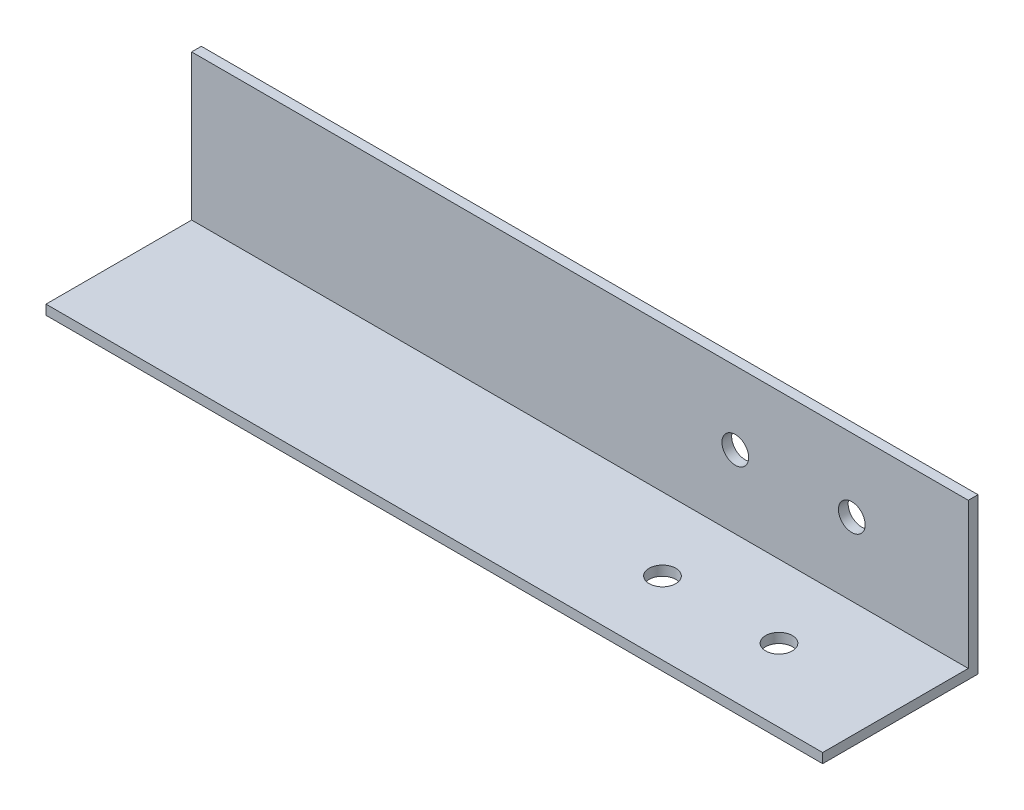
SolidWorks part; units mm, degrees
ref_plane "Front Plane" through (0, 0, 0) normal (0, 0, 1) x (1, 0, 0)
ref_plane "Top Plane" through (0, 0, 0) normal (0, 1, 0) x (1, 0, 0)
ref_plane "Right Plane" through (0, 0, 0) normal (1, 0, 0) x (0, 0, -1)
sketch "Sketch1" plane through (0, 0, 0) normal (1, 0, 0) x (0, 0, -1)
  line L1 (-3.175, 0) -> (-50.8, 0)
  line L2 (0, 0) -> (0, -3.175)
  line L3 (0, -3.175) -> (-50.8, -3.175)
  line L4 (-50.8, 0) -> (-50.8, -3.175)
  line L6 (0, 0) -> (0, 47.625)
  line L7 (0, 47.625) -> (-3.175, 47.625)
  line L8 (-3.175, 0) -> (-3.175, 47.625)
  dimension "D1" = 3.175
  dimension "D2" = 50.8
  dimension "D3" = 50.8
  dimension "D4" = 3.175
extrude "Boss-Extrude1" add sketch "Sketch1" along normal blind 254
sketch "Sketch2" plane through (0, 0, 3.175) normal (0, 0, 1) x (1, 0, 0)
  line L0 (254, 23.8125) -> (0, 23.8125) construction
  line L1 (254, 47.625) -> (254, 0) construction
  line L2 (0, 47.625) -> (0, 0) construction
  circle A0 centre (177.8, 23.8125) radius 4.3656
  circle A1 centre (215.9, 23.8125) radius 4.3656
  point P10 (0, 0)
  point P12 (232.184, 63.5082)
  dimension "D1" = 8.7312
  dimension "D2" = 38.1
  dimension "D3" = 38.1
extrude "Cut-Extrude1" cut sketch "Sketch2" against normal up to surface (3.175 mm away) up to face at (127, 22.225, 0)
sketch "Sketch3" plane through (0, 0, 0) normal (0, 1, 0) x (1, 0, 0)
  line L0 (0, -26.9875) -> (254, -26.9875) construction
  line L1 (0, -3.175) -> (0, -50.8) construction
  line L2 (254, -3.175) -> (254, -50.8) construction
  circle A0 centre (177.8, -26.9875) radius 4.3656
  circle A1 centre (215.9, -26.9875) radius 4.3656
  dimension "D1" = 8.7312
  dimension "D2" = 38.1
  dimension "D3" = 38.1
extrude "Cut-Extrude2" cut sketch "Sketch3" against normal up to surface (3.175 mm away) up to face at (127, -3.175, 25.4)
